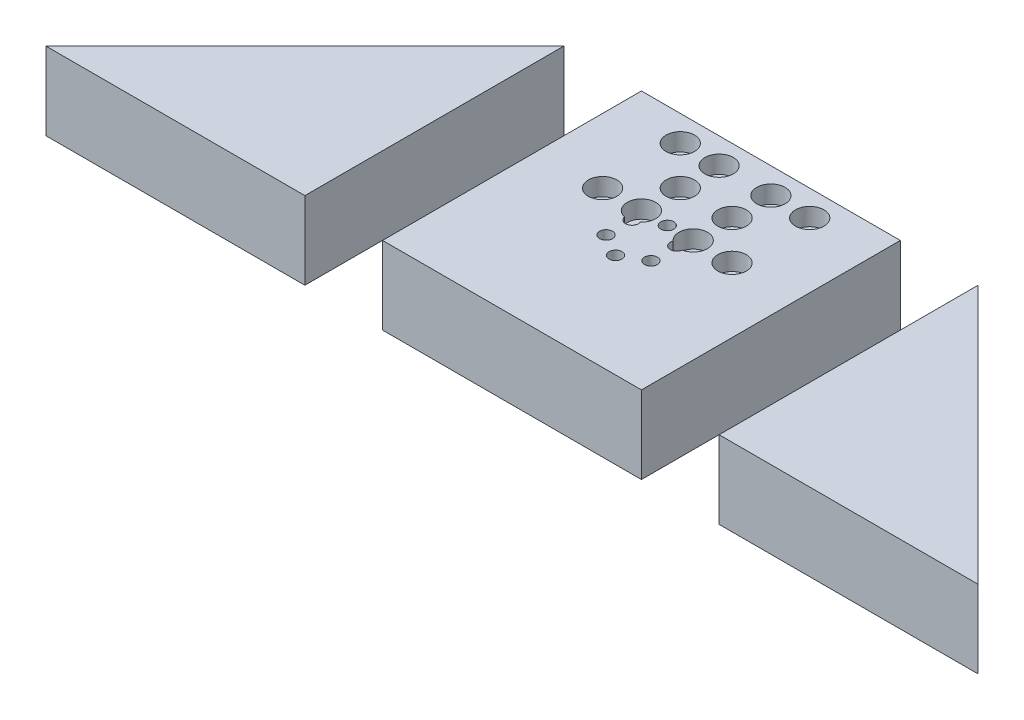
SolidWorks part; units mm, degrees
ref_plane "前视基准面" through (0, 0, 0) normal (0, 0, 1) x (1, 0, 0)
ref_plane "上视基准面" through (0, 0, 0) normal (0, 1, 0) x (1, 0, 0)
ref_plane "右视基准面" through (0, 0, 0) normal (1, 0, 0) x (0, 0, -1)
sketch "草图1" plane through (0, 0, 0) normal (0, 1, 0) x (1, 0, 0)
  line L0 (80, -50) -> (180, -50)
  line L1 (-50, -50) -> (50, -50)
  line L2 (-50, -50) -> (-50, 50)
  line L3 (-50, 50) -> (50, 50)
  line L4 (50, -50) -> (50, 50)
  line L5 (-50, -50) -> (50, 50) construction
  line L6 (-50, 50) -> (50, -50) construction
  line L7 (180, -50) -> (80, 50)
  line L8 (80, 50) -> (80, -50)
  point P0 (0, 0)
  dimension "D1" = 100
  dimension "D2" = 100
  dimension "D3" = 30
extrude "凸台-拉伸1" add sketch "草图1" along normal blind 30
hole_wizard "打孔尺寸(%根据)内六角圆柱头螺钉的类型1" positions "草图2" profile "草图4" counterbore size "M6" standard "GB" end condition through all
sketch "草图2" plane through (0, 30, 0) normal (0, 1, 0) x (1, 0, 0)
  line L0 (50, 50) -> (-50, 50) construction
  line L1 (-50, 50) -> (-50, -50) construction
  point P0 (-25, 10)
  dimension "D1" = 40
  dimension "D2" = 25
sketch "草图4" plane through (-25, 30, -10) normal (1, 0, 0) x (0, 0, 1)
  line L0 (0, 0) -> (0, 30)
  line L1 (0, 30) -> (3.3, 30)
  line L3 (3.3, 30) -> (3.3, 6.8)
  line L4 (3.3, 6.8) -> (5.5, 6.8)
  line L5 (5.5, 6.8) -> (5.5, 0)
  line L7 (5.5, 0) -> (0, 0)
  line L11 (0, -6.35) -> (0, 107.95) construction
  dimension "通孔孔直径" = 6.6
  dimension "通孔孔深度" = 30
  dimension "柱形沉头孔直径" = 11
  dimension "柱形沉头孔深度" = 6.8
hole_wizard "M6 螺纹孔1" positions "草图9" profile "草图11" tap size "M6" standard "GB" end condition through all
sketch "草图9" plane through (0, 30, 0) normal (0, 1, 0) x (1, 0, 0)
  line L0 (-25, 10) -> (0, 10)
  line L1 (0, 10) -> (0, 0)
  point P0 (0, 10)
cosmetic thread "孔螺蚊线1" parameters "D2"=6
sketch "草图11" plane through (0, 30, -10) normal (1, 0, 0) x (0, 0, 1)
  line L0 (0, 0) -> (0, 30)
  line L1 (0, 30) -> (2.5, 30)
  line L2 (2.5, 30) -> (2.5, 0)
  line L5 (2.5, 0) -> (0, 0)
  line L11 (0, -6.35) -> (0, 107.95) construction
  dimension "通孔螺纹孔钻头直径" = 5
  dimension "通孔螺纹孔钻头深度" = 30
pattern_linear "阵列(线性)1" count 2 spacing 15 along (1, 0, 0) count 3 spacing 15 along (0, 0, -1) skipping (0, 1) of "打孔尺寸(%根据)内六角圆柱头螺钉的类型1"
ref_axis "基准轴1" through (0, 0, 0) along (0, 1, 0)
pattern_circular "阵列(圆周)1" count 6 over 360 about axis through (0, 0, 0) along (0, 1, 0) of "M6 螺纹孔1"
mirror "镜向3" about plane through (0, 0, 0) normal (1, 0, 0) of "阵列(线性)1"
mirror "镜向5" about plane through (0, 0, 0) normal (1, 0, 0) of bodies 107
